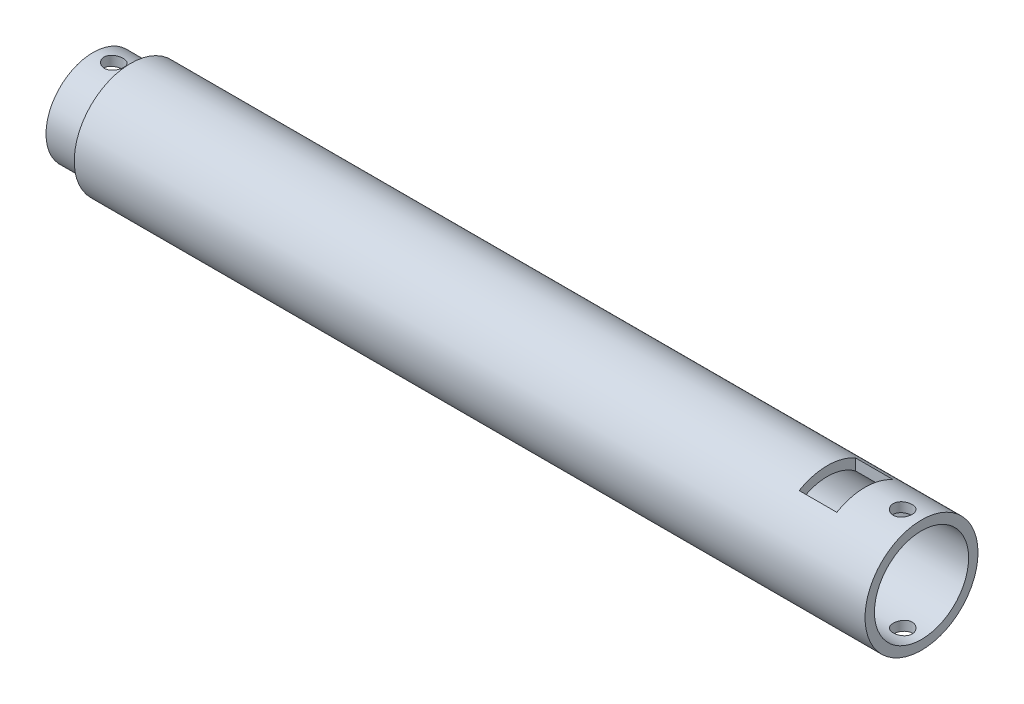
SolidWorks part; units mm, degrees
ref_plane "Plano frontal" through (0, 0, 0) normal (0, 0, 1) x (1, 0, 0)
ref_plane "Plano superior" through (0, 0, 0) normal (0, 1, 0) x (1, 0, 0)
ref_plane "Plano direito" through (0, 0, 0) normal (1, 0, 0) x (0, 0, -1)
sketch "Esboço1" plane through (0, 0, 0) normal (1, 0, 0) x (0, 0, -1)
  circle A0 centre (0, 0) radius 15
  circle A1 centre (0, 0) radius 12.5
  dimension "D1" = 30
  dimension "D2" = 25
extrude "Ressalto-extrusão1" add sketch "Esboço1" along normal blind 210 contours A1 | A0
sketch "Esboço2" plane through (0, 0, 0) normal (-1, 0, 0) x (0, 0, 1)
  line L0 (0, 15) -> (0, 0) construction
  circle A0 centre (0, 0) radius 15 construction
  circle A1 centre (0, 0) radius 10
  circle A3 centre (0, 0) radius 12.5
  dimension "D1" = 20
extrude "Ressalto-extrusão3" add sketch "Esboço2" against normal blind 15 from offset 10
sketch "Esboço4" plane through (0, 0, 0) normal (0, 1, 0) x (1, 0, 0)
  line L0 (-10, 12.5) -> (-10, -12.5) construction
  line L1 (210, -15) -> (210, 15) construction
  circle A0 centre (-5, 0.5) radius 2.5
  circle A1 centre (205, 0) radius 2.5
  dimension "D1" = 5
  dimension "D3" = 5
  dimension "D2" = 5
  dimension "D4" = 5
sketch "Esboço5" plane through (0, 0, 0) normal (0, 1, 0) x (1, 0, 0)
  line L0 (210, -15) -> (210, 15) construction
  circle A0 centre (205, 0) radius 2.5
  dimension "D1" = 5
  dimension "D2" = 5
sketch3d "3DSketch1"
  point P0 (150.2064, 4.5345, 11.6485)
extrude "Corte-extrusão2" cut sketch "Esboço4" against normal blind 300 and the other way blind 300 contours A1
extrude "Corte-extrusão3" cut sketch "Esboço4<3>" against normal blind 300 and the other way blind 300
sketch "Esboço4<3>" plane through (0, 0, 0) normal (0, 1, 0) x (1, 0, 0) same geometry as "Esboço4"
sketch "Esboço6" plane through (0, 0, 0) normal (0, 1, 0) x (1, 0, 0)
  line L0 (210, -15) -> (210, 15) construction
  line L1 (195, 7.5) -> (185, 7.5)
  line L2 (195, 7.5) -> (195, -7.5)
  line L3 (195, -7.5) -> (185, -7.5)
  line L4 (185, 7.5) -> (185, -7.5)
  line L5 (195, 7.5) -> (185, -7.5) construction
  line L6 (195, -7.5) -> (185, 7.5) construction
  line L7 (210, 15) -> (0, 15) construction
  point P0 (190, 0)
  point P5 (194.5623, 1.1624)
  point P6 (0, 0)
  dimension "D1" = 15
  dimension "D2" = 10
  dimension "D3" = 20
  dimension "D4" = 15
extrude "Corte-extrusão4" cut sketch "Esboço6" along normal blind 20
